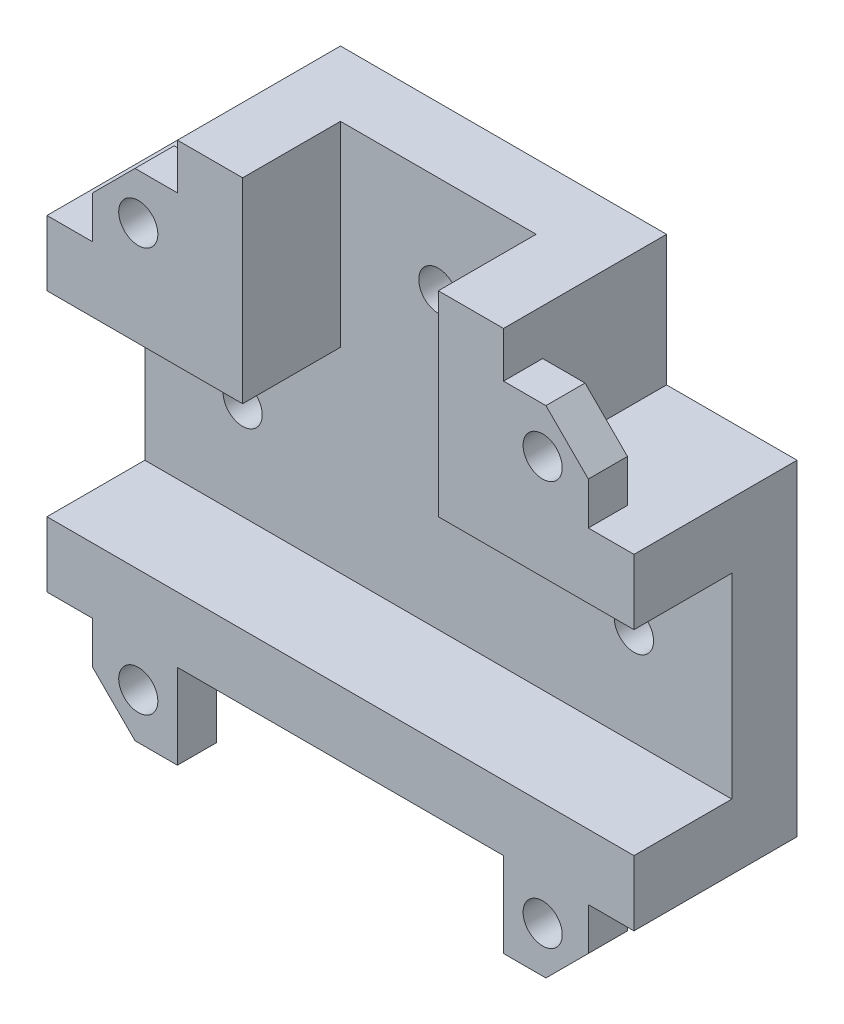
SolidWorks part; units mm, degrees
ref_plane "Front Plane" through (0, 0, 0) normal (0, 0, 1) x (1, 0, 0)
ref_plane "Top Plane" through (0, 0, 0) normal (0, 1, 0) x (1, 0, 0)
ref_plane "Right Plane" through (0, 0, 0) normal (1, 0, 0) x (0, 0, -1)
sketch "Sketch1" plane through (0, 0, 0) normal (0, 0, 1) x (1, 0, 0)
  line L0 (14.3137, 0.7353) -> (29.3137, 0.7353)
  line L1 (-15.6863, 0.7353) -> (-0.6863, 0.7353)
  line L2 (-15.6863, 0.7353) -> (-15.6863, -14.2647)
  line L3 (-15.6863, -14.2647) -> (29.3137, -14.2647)
  line L4 (29.3137, 0.7353) -> (29.3137, -14.2647)
  line L5 (-0.6863, 15.7353) -> (14.3137, 15.7353)
  line L6 (-0.6863, 15.7353) -> (-0.6863, 0.7353)
  line L8 (14.3137, 15.7353) -> (14.3137, 0.7353)
  dimension "D1" = 15
  dimension "D2" = 15
  dimension "D3" = 15
  dimension "D4" = 15
  dimension "D5" = 15
extrude "Boss-Extrude1" add sketch "Sketch1" along normal blind 5
sketch "Sketch2" plane through (0, 0, 0) normal (0, 0, -1) x (-1, 0, 0)
  line L0 (0.6863, 15.7353) -> (5.6863, 15.7353)
  line L1 (5.6863, 15.7353) -> (5.6863, 5.7353)
  line L2 (15.6863, 0.7353) -> (15.6863, 5.7353)
  line L3 (15.6863, 5.7353) -> (6.08, 5.7353)
  line L4 (15.6863, 0.7353) -> (0.6863, 0.7353)
  line L5 (0.6863, 15.7353) -> (0.6863, 0.7353)
  line L6 (6.08, 5.7353) -> (5.6863, 5.7353)
  dimension "D1" = 5
  dimension "D2" = 5
extrude "Boss-Extrude2" add sketch "Sketch2" against normal blind 12.5 contours L3 L6 L1 L0 L5 L4 L2
sketch "Sketch4" plane through (0, 0, 0) normal (0, 0, -1) x (-1, 0, 0)
  line L0 (15.6863, -14.2647) -> (-29.3137, -14.2647)
  line L1 (-29.3137, -14.2647) -> (-29.3137, -19.2647)
  line L2 (-29.3137, -19.2647) -> (15.6863, -19.2647)
  line L3 (15.6863, -19.2647) -> (15.6863, -14.2647)
  dimension "D1" = 5
extrude "Boss-Extrude3" add sketch "Sketch4" against normal blind 12.5
ref_plane "Plane4" through (6.8137, 0, 0) normal (-1, 0, 0) x (0, 0, 1)
ref_plane "Plane5" through (-5.6863, 0, 0) normal (-1, 0, 0) x (0, 0, 1)
mirror "Mirror1" about plane through (6.8137, 0, 0) normal (-1, 0, 0) of "Boss-Extrude2"
sketch "Sketch6" plane through (0, 0, 5) normal (0, 0, 1) x (1, 0, 0)
  line L0 (6.8137, 5.5) -> (6.8137, -5.5) construction
  line L1 (-15.6863, 0.7353) -> (-15.6863, -14.2647) construction
  line L2 (-15.6863, 0.7353) -> (-0.6863, 0.7353) construction
  line L3 (29.3137, 0.7353) -> (14.3137, 0.7353) construction
  line L5 (29.3137, -14.2647) -> (29.3137, 0.7353) construction
  line L6 (14.3137, 15.7353) -> (-0.6863, 15.7353) construction
  circle A0 centre (6.8137, 8.2353) radius 1.5
  circle A1 centre (-8.1863, -6.7647) radius 1.5
  circle A2 centre (21.8137, -6.7647) radius 1.5
  dimension "D1" = 3
  dimension "D2" = 3
  dimension "D3" = 3
  dimension "D5" = 7.5
  dimension "D7" = 7.5
  dimension "D8" = 7.5
  dimension "D4" = 7.5
  dimension "D6" = 7.5
ref_plane "Plane6" through (-5.6863, 5.7353, 12.5) normal (0, -1, 0) x (-1, 0, 0)
sketch "Sketch13" plane through (0, 0, 12.5) normal (0, 0, 1) x (1, 0, 0)
  line L0 (-8.9363, 12.2353) -> (-12.1863, 8.9853)
  line L2 (-5.6863, 12.2353) -> (-5.6863, 5.7353)
  line L4 (-5.6863, 5.7353) -> (-12.1863, 5.7353)
  line L5 (-5.6863, 12.2353) -> (-8.9363, 12.2353)
  line L6 (-12.1863, 8.9853) -> (-12.1863, 5.7353)
extrude "Boss-Extrude5" add sketch "Sketch13" against normal blind 3
sketch "Sketch14" plane through (0, 0, 12.5) normal (0, 0, 1) x (1, 0, 0)
  line L0 (-5.6863, 5.5) -> (-5.6863, -5.5) construction
  line L1 (-15.6863, 5.7353) -> (-12.1863, 5.7353) construction
  circle A0 centre (-8.6863, 8.7353) radius 1.5
  dimension "D1" = 3
  dimension "D2" = 3
  dimension "D3" = 3
extrude "Cut-Extrude2" cut sketch "Sketch14" against normal through all
mirror "Mirror9" about plane through (6.8137, 0, 0) normal (-1, 0, 0) of "Boss-Extrude5", "Cut-Extrude2"
extrude "Cut-Extrude3" cut sketch "Sketch6" against normal through all
ref_plane "基准面1" through (0, -6.7647, 0) normal (0, 1, 0) x (1, 0, 0)
mirror "镜向1" about plane through (0, -6.7647, 0) normal (0, 1, 0) of "Mirror9", "Cut-Extrude2", "Boss-Extrude5"
